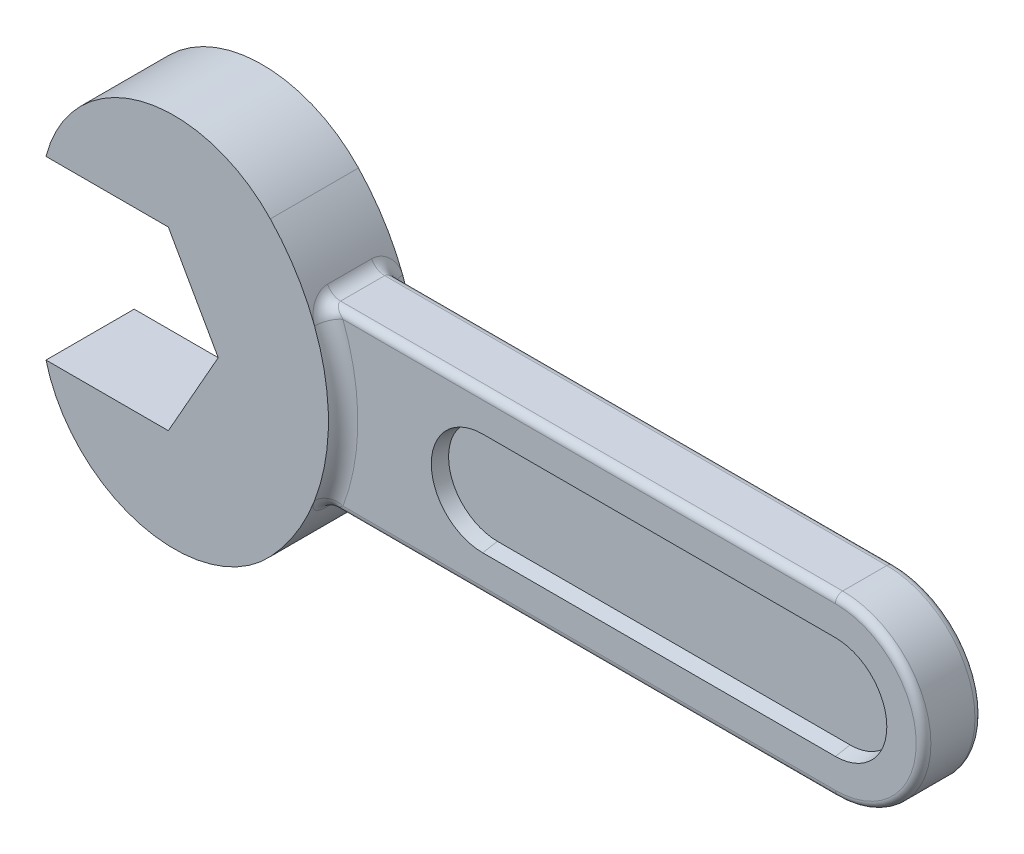
SolidWorks part; units mm, degrees
note: The reader was unsure of these and kept them because the rebuilt part matched: shared geometry of "Sketch3<5>", "Sketch3<6>".
material "AISI 1020"
ref_plane "Front Plane" through (0, 0, 0) normal (0, 0, 1) x (1, 0, 0)
ref_plane "Top Plane" through (0, 0, 0) normal (0, 1, 0) x (1, 0, 0)
ref_plane "Right Plane" through (0, 0, 0) normal (1, 0, 0) x (0, 0, -1)
sketch "Sketch1" plane through (0, 0, 0) normal (0, 0, 1) x (1, 0, 0)
  line L0 (-14.9879, 19.05) -> (11.4476, 19.05)
  line L1 (11.4476, 19.05) -> (22.225, 0)
  line L2 (22.225, 0) -> (11.4476, -19.05)
  line L3 (11.4476, -19.05) -> (-14.9879, -19.05)
  circle A0 centre (0, 0) radius 22.225 construction
  arc A1 (33.4818, -31.5978) -> (33.4818, 31.5978) centre (0, 0) ccw
  arc A3 (33.4818, 31.5978) -> (-14.9879, 19.05) centre (12.7, 11.9854) ccw
  arc A5 (-14.9879, -19.05) -> (33.4818, -31.5978) centre (12.7, -11.9854) ccw
  point P3 (-15.6175, -15.8128)
  point P10 (0, 0)
  point P12 (0, 0)
  point P13 (0, 0)
  point P17 (-14.9879, 20.5236)
  point P18 (-14.9879, -15.8128)
  point P19 (0, 0)
  point P20 (0, 0)
  dimension "D1" = 44.45
  dimension "D3" = 92.075
  dimension "D2" = 38.1
  dimension "D5" = 28.575
  dimension "D4" = 12.7
extrude "Boss-Extrude1" add sketch "Sketch1" along normal mid plane 19.05
sketch "Sketch3" plane through (0, 0, 0) normal (0, 0, 1) x (1, 0, 0)
  line L0 (76.2, 0) -> (152.4, 0) construction
  line L1 (76.2, 11.1125) -> (152.4, 11.1125)
  line L2 (76.2, -11.1125) -> (152.4, -11.1125)
  line L3 (152.4, -19.05) -> (41.9112, -19.05)
  line L4 (152.4, 19.05) -> (41.9112, 19.05)
  line L13 (11.4476, 19.05) -> (22.225, 0)
  line L14 (22.225, 0) -> (11.4476, -19.05)
  line L15 (11.4476, -19.05) -> (-14.9879, -19.05)
  line L16 (-14.9879, 19.05) -> (11.4476, 19.05)
  line L17 (11.4476, 19.05) -> (22.225, 0)
  line L18 (22.225, 0) -> (11.4476, -19.05)
  line L19 (11.4476, -19.05) -> (-14.9879, -19.05)
  line L20 (-14.9879, 19.05) -> (11.4476, 19.05)
  arc A0 (76.2, 11.1125) -> (76.2, -11.1125) centre (76.2, 0) ccw
  arc A1 (152.4, -11.1125) -> (152.4, 11.1125) centre (152.4, 0) ccw
  arc A2 (152.4, -19.05) -> (152.4, 19.05) centre (152.4, 0) ccw
  arc A3 (33.4818, -31.5978) -> (33.4818, 31.5978) centre (0, 0) ccw construction
  arc A10 (-14.9879, -19.05) -> (33.4818, -31.5978) centre (12.7, -11.9854) ccw
  arc A11 (33.4818, -31.5978) -> (33.4818, 31.5978) centre (0, 0) ccw
  arc A12 (33.4818, 31.5978) -> (-14.9879, 19.05) centre (12.7, 11.9854) ccw
  arc A13 (-14.9879, -19.05) -> (33.4818, -31.5978) centre (12.7, -11.9854) ccw
  arc A14 (33.4818, -31.5978) -> (33.4818, 31.5978) centre (0, 0) ccw
  arc A15 (33.4818, 31.5978) -> (-14.9879, 19.05) centre (12.7, 11.9854) ccw
  point P2 (114.3, 0)
  point P13 (0, 0)
  point P17 (0, 0)
  point P18 (0, 0)
  point P20 (0, 0)
  dimension "D1" = 11.1125
  dimension "D2" = 38.1
  dimension "D3" = 76.2
  dimension "D4" = 152.4
  dimension "D5" = 0
extrude "Boss-Extrude2" add sketch "Sketch3" along normal mid plane 12.7
extrude "Cut-Extrude1" cut sketch "Sketch3<5>" along normal blind 3.175 draft 10 from surface at -6.35
sketch "Sketch3<5>" plane through (0, 0, 0) normal (0, 0, 1) x (1, 0, 0) same geometry as "Sketch3"
extrude "Cut-Extrude2" cut sketch "Sketch3<6>" against normal blind 3.175 draft 10 from surface at 6.35 starting at face at (102.9497, 0, 6.35)
sketch "Sketch3<6>" plane through (0, 0, 0) normal (0, 0, 1) x (1, 0, 0) same geometry as "Sketch3"
fillet "Fillet1" radius 1.5875 6 edges at (97.1556, 19.05, -6.35) (171.45, 0, -6.35) (97.1556, 19.05, 6.35) (171.45, 0, 6.35) (97.1556, -19.05, -6.35) (97.1556, -19.05, 6.35)
fillet "Fillet2" radius 3.175 8 edges at (42.1476, -18.5212, -5.9454) (41.9112, -19.05, 0) (42.0456, -18.7514, 5.6893) (46.0375, 0, 6.35) (42.1476, 18.5212, 5.9454) (41.9112, 19.05, 0) (42.0456, 18.7514, -5.6893) (46.0375, 0, -6.35)
